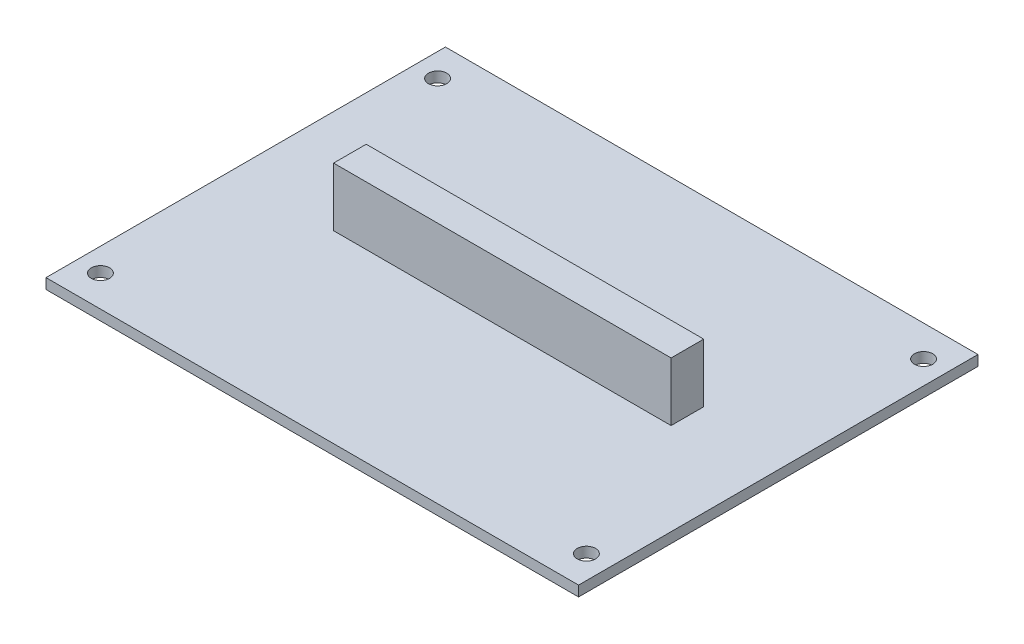
SolidWorks part; units mm, degrees
ref_plane "Front Plane" through (0, 0, 0) normal (0, 0, 1) x (1, 0, 0)
ref_plane "Top Plane" through (0, 0, 0) normal (0, 1, 0) x (1, 0, 0)
ref_plane "Right Plane" through (0, 0, 0) normal (1, 0, 0) x (0, 0, -1)
sketch "Sketch1" plane through (0, 0, 0) normal (0, 1, 0) x (1, 0, 0)
  line L0 (-36.5, 25.325) -> (-36.5, -25.325) construction
  line L1 (-40, -30) -> (40, -30)
  line L2 (-40, -30) -> (-40, 30)
  line L3 (-40, 30) -> (40, 30)
  line L4 (40, -30) -> (40, 30)
  line L5 (-40, -30) -> (40, 30) construction
  line L6 (-40, 30) -> (40, -30) construction
  line L7 (-36.5, 25.325) -> (36.5, 25.325) construction
  circle A4 centre (-36.5, 25.325) radius 1.375
  circle A5 centre (-36.5, -25.325) radius 1.375
  circle A6 centre (36.5, -25.325) radius 1.375
  circle A7 centre (36.5, 25.325) radius 1.375
  point P0 (0, 0)
  point P6 (0, 25.325)
  point P7 (-36.5, 0)
  dimension "D5" = 2.75
  dimension "D1" = 80
  dimension "D2" = 60
  dimension "D3" = 73
  dimension "D4" = 50.65
extrude "Boss-Extrude1" add sketch "Sketch1" along normal blind 1.55
sketch "Sketch2" plane through (0, 1.55, 0) normal (0, 1, 0) x (1, 0, 0)
  line L0 (-24.5, 2.6) -> (26.2, 2.6)
  line L1 (26.2, 2.6) -> (26.2, -2.3)
  line L2 (26.2, -2.3) -> (-24.5, -2.3)
  line L3 (-24.5, -2.3) -> (-24.5, 2.6)
  line L4 (40, 30) -> (-40, 30) construction
  line L5 (-40, -30) -> (40, -30) construction
  line L6 (40, -30) -> (40, 30) construction
  line L7 (-40, 30) -> (-40, -30) construction
  dimension "D1" = 32.3
  dimension "D2" = 32.6
  dimension "D3" = 64.5
  dimension "D4" = 66.2
extrude "Boss-Extrude2" add sketch "Sketch2" along normal blind 8.8
